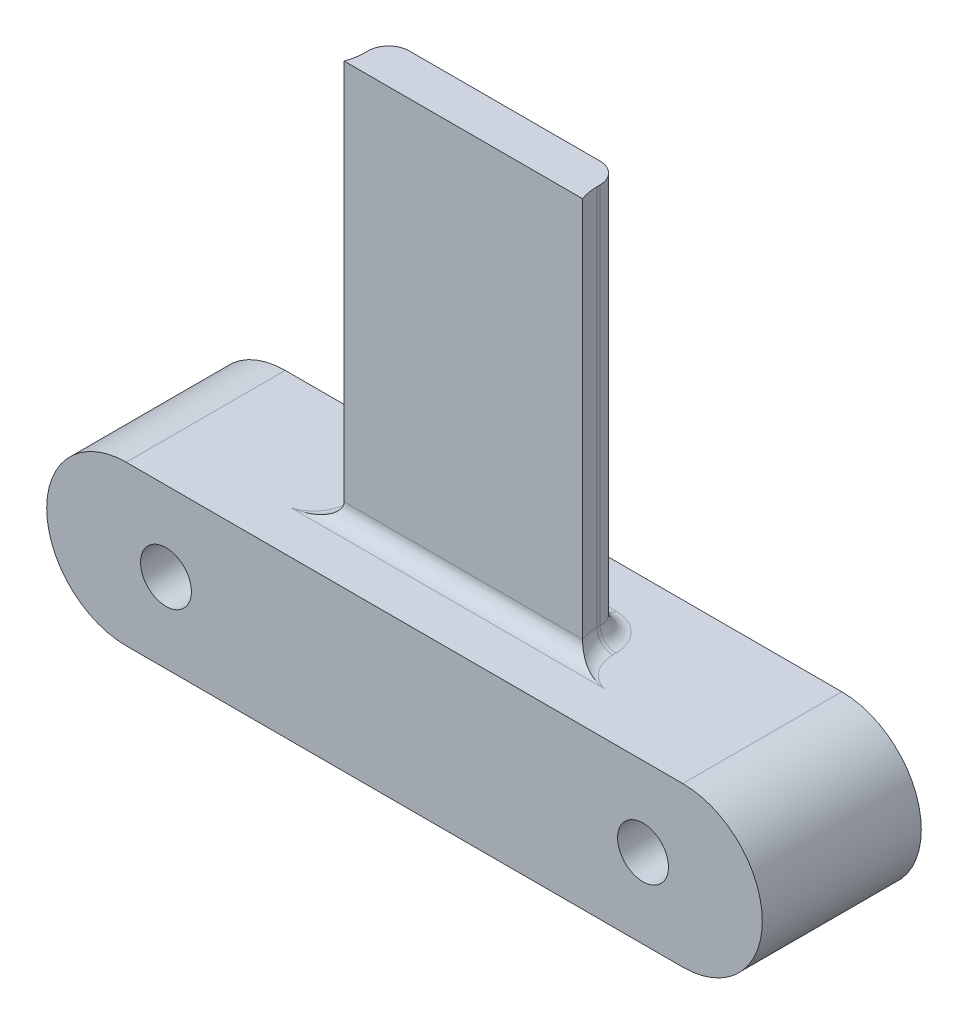
SolidWorks part; units mm, degrees
material "PETG"
ref_plane "Спереди" through (0, 0, 0) normal (0, 0, 1) x (1, 0, 0)
ref_plane "Сверху" through (0, 0, 0) normal (0, 1, 0) x (1, 0, 0)
ref_plane "Справа" through (0, 0, 0) normal (1, 0, 0) x (0, 0, -1)
sketch "Эскиз1" plane through (0, 0, 0) normal (0, 0, 1) x (1, 0, 0)
  line L0 (-22.5, 0) -> (22.5, 0) construction
  line L1 (-22.5, -5) -> (22.5, -5)
  line L2 (-22.5, -5) -> (-22.5, 5)
  line L3 (-22.5, 5) -> (22.5, 5)
  line L4 (22.5, -5) -> (22.5, 5)
  line L5 (-22.5, -5) -> (22.5, 5) construction
  line L6 (-22.5, 5) -> (22.5, -5) construction
  line L7 (0, 5) -> (0, -5) construction
  circle A0 centre (-15, 0) radius 1.6
  circle A1 centre (15, 0) radius 1.6
  point P0 (0, 0)
  dimension "D1" = 3.2
  dimension "D2" = 15
  dimension "D3" = 45
  dimension "D4" = 10
extrude "Бобышка-Вытянуть1" add sketch "Эскиз1" along normal mid plane 10
fillet "Скругление1" 2 edges at (-22.5, 5, 0) (-22.5, -5, 0) type full round first side face at (0, 5, 0) second side face at (0, -5, 0) middle face at (-22.5, 0, 0)
fillet "Скругление2" 2 edges at (22.5, 5, 0) (22.5, -5, 0) type full round first side face at (2.5, 5, 0) second side face at (2.5, -5, 0) middle face at (22.5, 0, 0)
sketch "Эскиз2" plane through (0, 5, 0) normal (0, 1, 0) x (1, 0, 0)
  line L0 (0, 5) -> (0, -5) construction
  line L1 (17.5, 5) -> (-17.5, 5) construction
  line L2 (17.5, -5) -> (-17.5, -5) construction
  line L3 (-17.5, 0) -> (17.5, 0) construction
  line L4 (-17.5, 5) -> (-17.5, -5) construction
  line L5 (17.5, -5) -> (17.5, 5) construction
  line L6 (-6, 2) -> (6, 2)
  line L7 (-8, 0) -> (-8, -0.2)
  line L8 (8, 0) -> (8, -0.2)
  line L10 (-8.7651, -2) -> (8.7651, -2)
  line L11 (-6, 1.3) -> (6, 1.3)
  line L12 (7.3, 0) -> (7.3, -0.2)
  line L13 (-7.495, -1.3) -> (7.495, -1.3)
  line L14 (-7.3, 0) -> (-7.3, -0.2)
  arc A0 (-6, 2) -> (-8, 0) centre (-6, 0) ccw
  arc A1 (-8, -0.2) -> (-8.7651, -2) centre (-10.5, -0.2) cw
  arc A2 (6, 2) -> (8, 0) centre (6, 0) cw
  arc A3 (8, -0.2) -> (8.7651, -2) centre (10.5, -0.2) ccw
  arc A4 (6, 1.3) -> (7.3, 0) centre (6, 0) cw
  arc A5 (7.3, -0.2) -> (7.495, -1.3) centre (10.5, -0.2) ccw
  arc A6 (-7.3, -0.2) -> (-7.495, -1.3) centre (-10.5, -0.2) cw
  arc A7 (-6, 1.3) -> (-7.3, 0) centre (-6, 0) ccw
  point P26 (0, 2)
  dimension "D3" = 2.5
  dimension "D1" = 4
  dimension "D2" = 16
  dimension "D4" = 0.2
  dimension "D5" = 4
  dimension "D6" = 0.7
extrude "Бобышка-Вытянуть2" add sketch "Эскиз2" along normal blind 25 contours L11 A7 L14 A6 L13 A5 L12 A4 region at (0, 5, 0.0235)
fillet "Скругление8" radius 1 8 edges at (7.3491, 5, 0.7586) (7.3, 5, 0.1) (6.9192, 5, -0.9192) (0, 5, -1.3) (-6.9192, 5, -0.9192) (-7.3, 5, 0.1) (-7.3491, 5, 0.7586) (0, 5, 1.3)
sketch "Эскиз3" plane through (0, 30, 0) normal (0, 1, 0) x (1, 0, 0)
  line L0 (6, 0.3) -> (-6, 0.3)
  line L1 (-6.3, 0) -> (-6.3, -0.2)
  line L2 (-6.3012, -0.3) -> (6.3012, -0.3)
  line L3 (6.3, -0.2) -> (6.3, 0)
  line L4 (6, 1.3) -> (-6, 1.3)
  line L5 (-7.3, 0) -> (-7.3, -0.2)
  line L6 (-7.495, -1.3) -> (7.495, -1.3)
  line L7 (7.3, -0.2) -> (7.3, 0)
  line L8 (6, 1.3) -> (-6, 1.3)
  line L9 (-7.3, 0) -> (-7.3, -0.2)
  line L10 (-7.495, -1.3) -> (7.495, -1.3)
  line L11 (7.3, -0.2) -> (7.3, 0)
  arc A0 (-6, 0.3) -> (-6.3, 0) centre (-6, 0) ccw
  arc A1 (-6.3012, -0.3) -> (-6.3, -0.2) centre (-10.5, -0.2) ccw
  arc A2 (6.3, -0.2) -> (6.3012, -0.3) centre (10.5, -0.2) ccw
  arc A3 (6.3, 0) -> (6, 0.3) centre (6, 0) ccw
  arc A4 (-6, 1.3) -> (-7.3, 0) centre (-6, 0) ccw
  arc A5 (-7.495, -1.3) -> (-7.3, -0.2) centre (-10.5, -0.2) ccw
  arc A6 (7.3, -0.2) -> (7.495, -1.3) centre (10.5, -0.2) ccw
  arc A7 (7.3, 0) -> (6, 1.3) centre (6, 0) ccw
  arc A8 (-6, 1.3) -> (-7.3, 0) centre (-6, 0) ccw
  arc A9 (-7.495, -1.3) -> (-7.3, -0.2) centre (-10.5, -0.2) ccw
  arc A10 (7.3, -0.2) -> (7.495, -1.3) centre (10.5, -0.2) ccw
  arc A11 (7.3, 0) -> (6, 1.3) centre (6, 0) ccw
  dimension "D1" = 0
  dimension "D2" = 1
extrude "Вырез-Вытянуть1" cut sketch "Эскиз3" against normal blind 10 from offset 20 contours L3 A3 L0 A0 L1 A1 L2 A2 region at (0, 30, 0.0012) offset against normal yes
equation "\"DTailTube\"= 16mm'Диаметр трубки хвостового оперения"
equation "\"FusLenght\"= 700mm"
equation "\"DMotor\"= 35.2mm"
equation "\"MotorArm\"= 320mm"
equation "\"DFus\"= 150mm"
equation "\"DFusTube\"= 30mm'Диаметр трубки внутри фюзеляжа"
equation "\"FusTubeHeight\"= 40mm"
equation "\"FusCentralPartLenght\"= 410mm"
equation "\"FusNoseLenght\"= 150mm"
equation "\"WingOffset\"= 1mm'Расстояние от внутренней поверхности фюзеляжа до профиля крыла по вертикали"
equation "\"EllipseRatio\"= 0.95'Центральная часть фюзеляжа - эллипс. Этот параметр - отношение длин осей эллипса"
equation "\"FrameOffset\"= 0.6mm"
equation "\"DThreadedInsert\"= 3mm'Внешний диамер резьбовых втулок"
equation "\"CenterSectionLenght\"= 140mm'Длина центроплана"
equation "\"b\"= 1700mm'Размах"
equation "\"cwr\"= 236mm'Корневая хорда крыла"
equation "\"TR\"= 0.75'Сужение крыла"
equation "\"cwt\"= \"TR\" * \"cwr\"'Концевая хорда крыла"
equation "\"DWingMainSpar\"= 16mm'Диаметр главного лонжерона крыла"
equation "\"DWingSecondSpar\"= 8mm'Диаметр второго лонжерона крыла"
equation "\"WingSparsDistance\"= 80mm'Расстояния между отверстиями по лонжерон крыла"
equation "\"c\"= 210mm'САХ крыла"
equation "\"FusTubeLenght\"= \"FusLenght\"-90mm'Длина трубки фюзеляжа"
equation "\"bt\"=291mm'Высота лопатки хвоста"
equation "\"TailTubeLenght\"=680mm'Длина хвостовой балки"
equation "\"DStringer\"=6mm'Диаметр стрингеров"
equation "\"TailConnectorBaseLenght\"=20mm'Высота основания конектора хвоста"
equation "\"CargoHolderHoleDistance\"=30mm'Расстояние между крепежными отверстиями для держателя груза"
equation "\"D2@Эскиз1\"=\"CargoHolderHoleDistance\"/2"
equation "\"D3@Эскиз1\"=\"CargoHolderHoleDistance\"+15"
equation "\"ct\"=182mm'Корневая хорда хвоста"
equation "\"lambda_t\"=0.3'Доля хвоста, занатая рулем высоты"
equation "\"FuselageThickness\"=1.2mm'Толщина фюзеляжа"
equation "\"DTailSpar\"=6mm'Диаметр лонжерона хвостового оперения"
equation "\"TailSparDistance\"=40mm'Расстояние между лонжеронами хвостового оперения"
equation "\"CrossSectionWidth\"=15mm'Ширина кольцевой части шпангоута"
